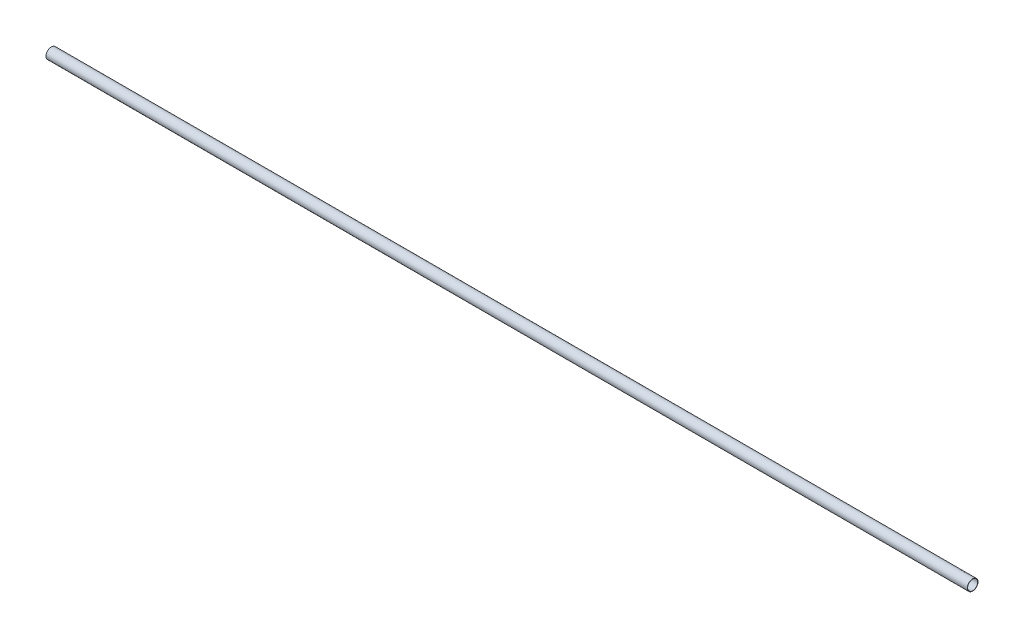
SolidWorks part; units mm, degrees
ref_plane "Plano frontal" through (0, 0, 0) normal (0, 0, 1) x (1, 0, 0)
ref_plane "Plano superior" through (0, 0, 0) normal (0, 1, 0) x (1, 0, 0)
ref_plane "Plano direito" through (0, 0, 0) normal (1, 0, 0) x (0, 0, -1)
sketch3d "3DSketch1"
  line L0 (-31937.4493, -17298.2109, 40477.5488) -> (-34516.4702, -17298.2109, 40477.5488)
  line L1 (-31937.4493, -17298.2109, 41543.1604) -> (-31937.4493, -17298.2109, 39237.3639) construction
  point P4 (-34893.335, -17298.2109, 40489.1981)
  point P5 (-34633.7206, -17298.2109, 40477.5488)
  point P6 (-34536.4702, -17298.2109, 40477.5488)
sweep "Sweep-Thin1" add path "3DSketch1" circular profile diameter 30 parameters "D1"=1, "D3"=30
